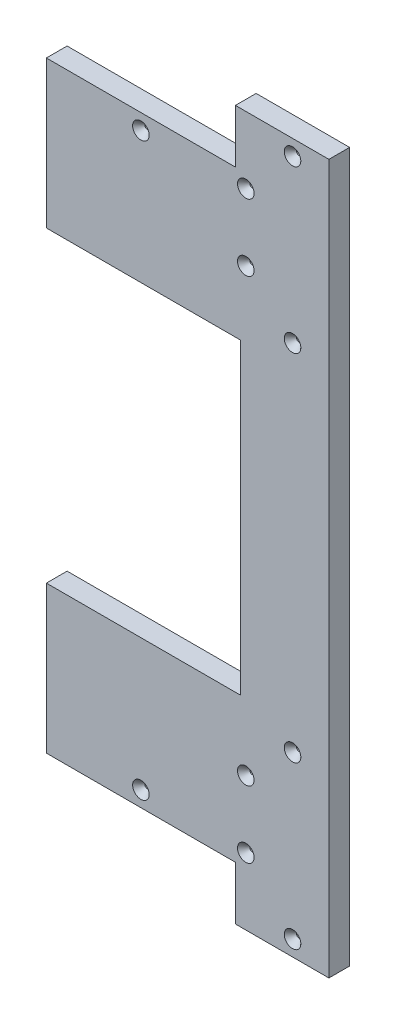
SolidWorks part; units mm, degrees
material "Beech"
ref_plane "Front Plane" through (0, 0, 0) normal (0, 0, 1) x (1, 0, 0)
ref_plane "Top Plane" through (0, 0, 0) normal (0, 1, 0) x (1, 0, 0)
ref_plane "Right Plane" through (0, 0, 0) normal (1, 0, 0) x (0, 0, -1)
sketch "Sketch1" plane through (0, 0, 0) normal (0, 0, 1) x (1, 0, 0)
  line L1 (-81.8518, 217.3) -> (116.731, 217.3)
  line L2 (-81.8518, 217.3) -> (-81.8518, -217.3)
  line L3 (-81.8518, -217.3) -> (116.731, -217.3)
  line L4 (116.731, 217.3) -> (116.731, -217.3)
  line L5 (72.1361, 217.3) -> (161.737, 217.3) construction
  point P8 (40.3861, -217.3)
extrude "Boss-Extrude1" add sketch "Sketch1" along normal blind 12.7
sketch "Sketch2" plane through (0, 0, 0) normal (0, 0, -1) x (-1, 0, 0)
  line L1 (-59.4361, 184.525) -> (81.8518, 184.525)
  line L2 (-59.4361, 184.525) -> (-59.4361, 217.3)
  line L3 (-59.4361, 217.3) -> (81.8518, 217.3)
  line L4 (81.8518, 184.525) -> (81.8518, 217.3)
  line L5 (-59.4361, -184.525) -> (81.8518, -184.525)
  line L6 (-59.4361, -184.525) -> (-59.4361, -217.3)
  line L7 (-59.4361, -217.3) -> (81.8518, -217.3)
  line L8 (81.8518, -184.525) -> (81.8518, -217.3)
extrude "Cut-Extrude1" cut sketch "Sketch2" against normal up to next
sketch "Sketch3" plane through (0, 0, 12.7) normal (0, 0, 1) x (1, 0, 0)
  line L0 (-81.8518, 184.525) -> (-81.8518, -184.525) construction
  line L1 (59.4361, 91.075) -> (-81.8518, 91.075) construction
  line L2 (59.4361, 91.075) -> (59.4361, -91.075) construction
  line L3 (59.4361, -91.075) -> (-81.8518, -91.075) construction
  line L4 (-81.8518, 91.075) -> (-81.8518, -91.075) construction
  line L5 (-81.8518, 91.075) -> (59.4361, 91.075) construction
  line L6 (-81.8518, -91.075) -> (59.4361, -91.075) construction
  line L7 (59.4361, 165.475) -> (59.4361, -165.475) construction
  line L8 (62.6111, 94.25) -> (-56.4518, 94.25)
  line L9 (-85.0268, 94.25) -> (-85.0268, -94.25)
  line L10 (62.6111, -94.25) -> (-56.4518, -94.25)
  line L11 (62.6111, 94.25) -> (62.6111, -94.25)
  line L12 (-81.8518, 94.25) -> (-85.0268, 94.25)
  line L13 (-81.8518, 184.525) -> (-56.4518, 184.525)
  line L14 (-81.8518, 184.525) -> (-81.8518, 94.25)
  line L16 (-56.4518, 184.525) -> (-56.4518, 94.25)
  line L17 (62.6111, 94.25) -> (-85.0268, 94.25) construction
  line L18 (-81.8518, -94.25) -> (-85.0268, -94.25)
  line L19 (-81.8518, -184.525) -> (-56.4518, -184.525)
  line L20 (-81.8518, -184.525) -> (-81.8518, -94.25)
  line L22 (-56.4518, -184.525) -> (-56.4518, -94.25)
  line L23 (62.6111, -94.25) -> (-85.0268, -94.25) construction
  dimension "D2" = 25.4
  dimension "D1" = 3.175
extrude "Cut-Extrude2" cut sketch "Sketch3" against normal up to next
hole_wizard "Hole1" positions "Sketch4" profile "Sketch5" legacy
sketch "Sketch4" plane through (449.8285, 0, 12.7) normal (0, 0, 1) x (0, 1, 0)
  line L0 (207.775, 377.6924) -> (207.775, 333.0975) construction
  line L4 (108.65, 377.6924) -> (108.65, 333.0975) construction
  line L8 (175, 506.2803) -> (175, 390.3924) construction
  line L12 (94.25, 390.3924) -> (94.25, 377.6924) construction
  line L17 (94.25, 384.0424) -> (217.3, 384.0424) construction
  line L19 (94.25, 384.0424) -> (135.2667, 384.0424)
  line L20 (135.2667, 384.0424) -> (176.2833, 384.0424)
  line L21 (176.2833, 384.0424) -> (217.3, 384.0424)
  line L22 (0, 333.0975) -> (0, 390.3924) construction
  point P39 (108.65, 355.3949)
  point P41 (207.775, 355.3949)
  point P43 (175, 448.3363)
  point P47 (135.2667, 384.0424)
  point P49 (176.2833, 384.0424)
  point P65 (-175, 448.3363)
  point P66 (-135.2667, 384.0424)
  point P67 (-176.2833, 384.0424)
  point P68 (-207.775, 355.3949)
  point P69 (-108.65, 355.3949)
sketch "Sketch5" plane through (94.4335, -108.65, 12.7) normal (1, 0, 0) x (0, -1, 0)
  line L0 (0, 0) -> (0, 39.0539)
  line L1 (0, 39.0539) -> (1.5875, 38.1)
  line L2 (1.5875, 38.1) -> (1.5875, 4.0177)
  line L3 (1.5875, 4.0177) -> (5.08, 0)
  line L4 (5.08, 0) -> (0, 0)
  line L5 (0, -14.3089) -> (0, 102.4216) construction
  line L6 (0, 39.0539) -> (-1.5875, 38.1) construction
  line L7 (-1.5875, 4.0177) -> (-5.08, 0) construction
  dimension "Diameter" = 3.175
  dimension "Depth" = 38.1
  dimension "C-Sink Diameter" = 10.16
  dimension "C-Sink Angle" = 82
  dimension "Drill Angle" = 118
